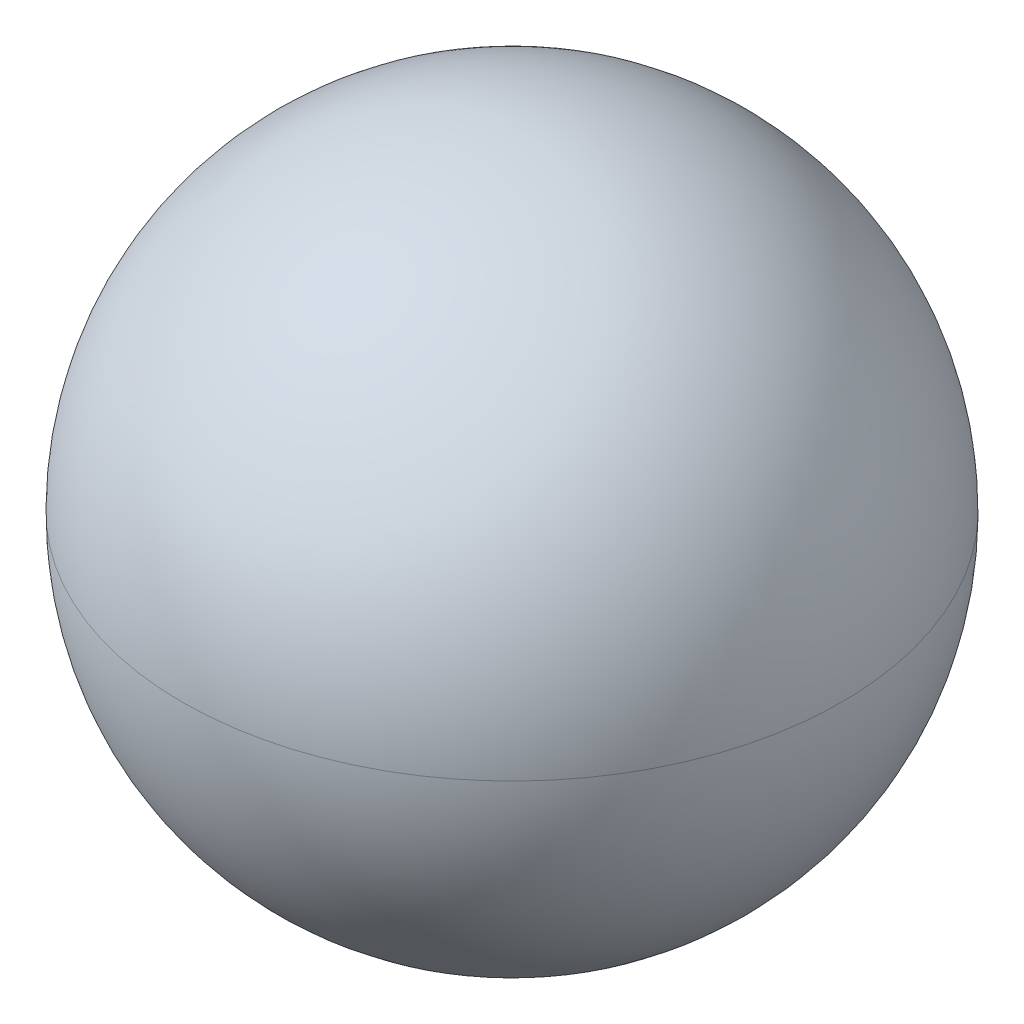
SolidWorks part; units mm, degrees
material "Foam"
ref_plane "Front Plane" through (0, 0, 0) normal (0, 0, 1) x (1, 0, 0)
ref_plane "Top Plane" through (0, 0, 0) normal (0, 1, 0) x (1, 0, 0)
ref_plane "Right Plane" through (0, 0, 0) normal (1, 0, 0) x (0, 0, -1)
sketch "Sketch1" plane through (0, 0, 0) normal (0, 1, 0) x (1, 0, 0)
  circle A0 centre (0, 0) radius 88.9
extrude "Boss-Extrude1" add sketch "Sketch1" along normal blind 177.8
fillet "Fillet1" radius 88.9 1 edges at (0, 177.8, 88.9)
fillet "Fillet2" radius 88.9 1 edges at (0, 0, 88.9)
